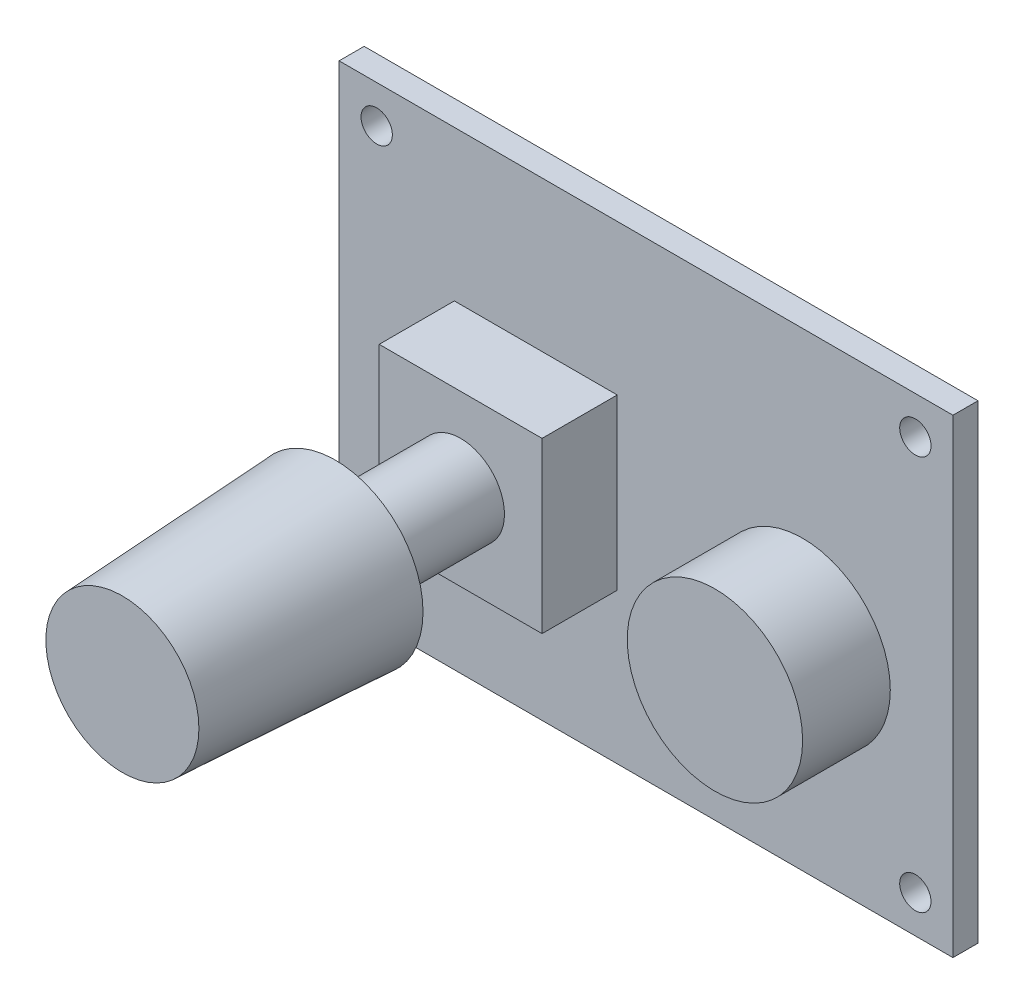
SolidWorks part; units mm, degrees
ref_plane "Спереди" through (0, 0, 0) normal (0, 0, 1) x (1, 0, 0)
ref_plane "Сверху" through (0, 0, 0) normal (0, 1, 0) x (1, 0, 0)
ref_plane "Справа" through (0, 0, 0) normal (1, 0, 0) x (0, 0, -1)
sketch "Эскиз1" plane through (0, 0, 0) normal (0, 0, 1) x (1, 0, 0)
  line L1 (-22.111, 16.0561) -> (26.889, 16.0561)
  line L2 (-22.111, 16.0561) -> (-22.111, -21.4439)
  line L3 (-22.111, -21.4439) -> (26.889, -21.4439)
  line L4 (26.889, 16.0561) -> (26.889, -21.4439)
  dimension "D1" = 49
  dimension "D2" = 37.5
extrude "Бобышка-Вытянуть1" add sketch "Эскиз1" along normal blind 2
sketch "Эскиз2" plane through (0, 0, 2) normal (0, 0, 1) x (1, 0, 0)
  line L0 (26.889, 16.0561) -> (-22.111, 16.0561) construction
  line L1 (-22.111, 16.0561) -> (-22.111, -21.4439) construction
  line L2 (26.889, -21.4439) -> (26.889, 16.0561) construction
  line L3 (-22.111, -21.4439) -> (26.889, -21.4439) construction
  circle A0 centre (-19.111, 13.0561) radius 1.25
  circle A1 centre (23.889, 13.0561) radius 1.25
  circle A2 centre (23.889, -18.4439) radius 1.25
  circle A3 centre (-19.111, -18.4439) radius 1.25
  dimension "D1" = 2.5
  dimension "D2" = 2.5
  dimension "D3" = 2.5
  dimension "D4" = 2.5
  dimension "D5" = 3
  dimension "D6" = 3
  dimension "D7" = 3
  dimension "D8" = 3
  dimension "D9" = 3
  dimension "D10" = 3
  dimension "D11" = 3
  dimension "D12" = 3
  dimension "D13" = 43
  dimension "D14" = 31.5
extrude "Вырез-Вытянуть1" cut sketch "Эскиз2" against normal through all
sketch "Эскиз3" plane through (0, 0, 2) normal (0, 0, 1) x (1, 0, 0)
  line L0 (-22.111, -21.4439) -> (26.889, -21.4439) construction
  line L1 (26.889, -21.4439) -> (26.889, 16.0561) construction
  circle A0 centre (14.889, -5.4439) radius 7
  dimension "D1" = 14
  dimension "D3" = 12
  dimension "D2" = 16
extrude "Бобышка-Вытянуть2" add sketch "Эскиз3" along normal blind 7
sketch "Эскиз4" plane through (0, 0, 2) normal (0, 0, 1) x (1, 0, 0)
  line L0 (-22.111, 16.0561) -> (-22.111, -21.4439) construction
  line L1 (-12.911, 4.0561) -> (0.089, 4.0561)
  line L2 (-12.911, 4.0561) -> (-12.911, -9.4439)
  line L3 (-12.911, -9.4439) -> (0.089, -9.4439)
  line L4 (0.089, 4.0561) -> (0.089, -9.4439)
  line L7 (-22.111, -21.4439) -> (26.889, -21.4439) construction
  dimension "D1" = 13.5
  dimension "D2" = 13
  dimension "D3" = 9.2
  dimension "D4" = 12
extrude "Бобышка-Вытянуть3" add sketch "Эскиз4" along normal blind 6
sketch "Эскиз5" plane through (0, 0, 8) normal (0, 0, 1) x (1, 0, 0)
  circle A0 centre (-6.411, -2.6939) radius 3.5
  dimension "D1" = 7
extrude "Бобышка-Вытянуть4" add sketch "Эскиз5" along normal blind 10
sketch "Эскиз6" plane through (0, 0, 18) normal (0, 0, 1) x (1, 0, 0)
  circle A0 centre (-6.411, -2.6939) radius 7
  dimension "D1" = 14
extrude "Бобышка-Вытянуть5" add sketch "Эскиз6" along normal blind 17 draft 3
